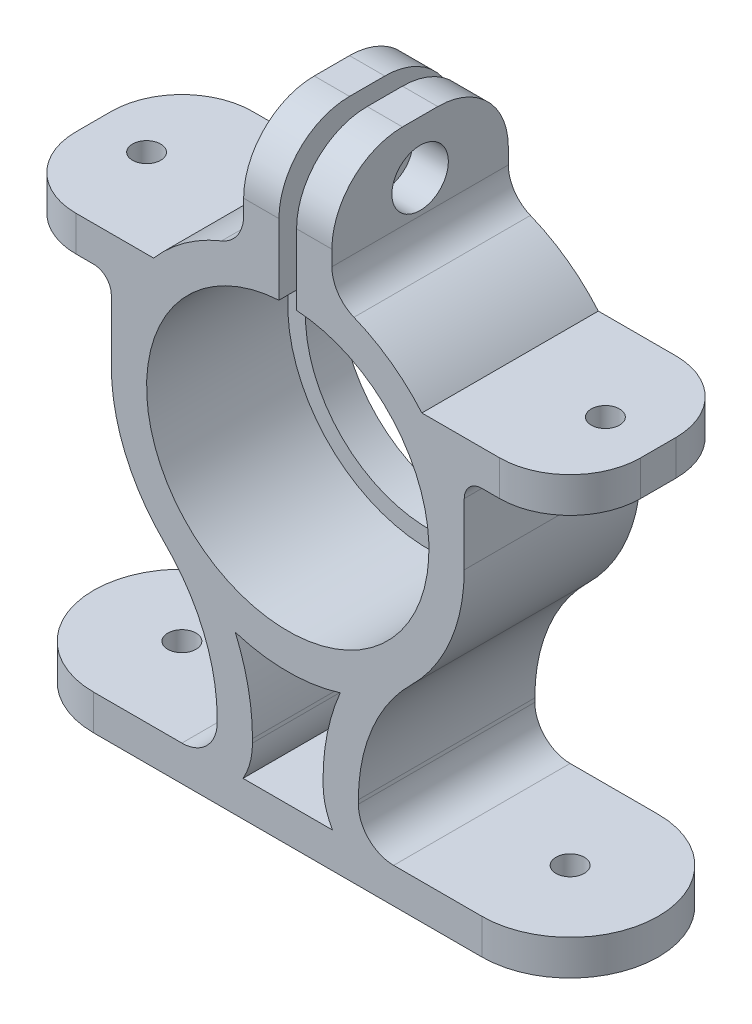
SolidWorks part; units mm, degrees
ref_plane "Front Plane" through (0, 0, 0) normal (0, 0, 1) x (1, 0, 0)
ref_plane "Top Plane" through (0, 0, 0) normal (0, 1, 0) x (1, 0, 0)
ref_plane "Right Plane" through (0, 0, 0) normal (1, 0, 0) x (0, 0, -1)
sketch "Sketch1" plane through (0, 0, 0) normal (0, 0, 1) x (1, 0, 0)
  line L0 (0, 0) -> (65.6061, 0) construction
  line L1 (32.8031, 0) -> (32.8031, 18.5) construction
  line L2 (12.0204, 18.5) -> (55.4995, 18.5) construction
  line L3 (16.803, 0) -> (48.8031, 0)
  line L4 (32.3031, 26.4843) -> (32.3031, 34.4875)
  line L5 (13.0695, 25) -> (55.8846, 25) construction
  line L6 (33.3031, 26.4843) -> (33.3031, 34.4875)
  line L7 (33.3031, 34.4875) -> (35.3032, 34.4875)
  line L8 (35.3032, 34.4875) -> (35.3032, 29.6243)
  line L9 (32.3031, 34.4875) -> (30.3031, 34.4875)
  line L10 (30.3031, 34.4875) -> (30.3031, 29.6243)
  line L11 (22.803, 22) -> (22.803, 18.5)
  line L12 (48.8031, 0) -> (48.8031, 2)
  line L13 (42.8031, 22) -> (42.8031, 18.5)
  line L14 (21.5003, 25) -> (16.803, 25)
  line L15 (16.803, 25) -> (16.803, 23)
  line L16 (16.803, 23) -> (21.803, 23)
  line L17 (44.1058, 25) -> (48.8031, 25)
  line L18 (48.8031, 23) -> (43.8031, 23)
  line L19 (48.8031, 25) -> (48.8031, 23)
  line L20 (16.803, 2) -> (26.803, 2)
  line L21 (16.803, 2) -> (16.803, 0)
  line L22 (28.803, 4) -> (28.803, 4.2171)
  line L23 (48.8031, 2) -> (38.8031, 2)
  line L24 (36.8031, 4) -> (36.8031, 4.2171)
  line L25 (44.1058, 25) -> (40.4025, 25)
  line L26 (21.5003, 25) -> (25.2036, 25)
  line L27 (35.7769, 8.9524) -> (35.7769, 8.9524)
  line L28 (35.7769, 8.9524) -> (35.7769, 8.9524)
  line L29 (35.7769, 8.9524) -> (35.7769, 8.9524)
  line L30 (35.7769, 8.9524) -> (35.7769, 8.9524)
  line L31 (35.7769, 8.9524) -> (35.7769, 8.9524)
  line L32 (35.7769, 8.9524) -> (35.7769, 8.9524)
  line L33 (35.7769, 8.9524) -> (35.7769, 8.9524)
  line L34 (35.7769, 8.9524) -> (35.7769, 8.9524)
  line L35 (34.8031, 4) -> (34.8031, 4.2171)
  line L36 (35.339, 2) -> (35.339, 2)
  line L37 (35.339, 2) -> (35.339, 2)
  line L38 (30.2671, 2) -> (35.339, 2)
  line L39 (30.2671, 2) -> (30.2671, 2)
  line L40 (30.2671, 2) -> (30.2671, 2)
  line L41 (30.803, 4) -> (30.803, 4.2171)
  line L42 (29.8292, 8.9524) -> (29.8292, 8.9524)
  line L43 (29.8292, 8.9524) -> (29.8292, 8.9524)
  line L44 (29.8292, 8.9524) -> (29.8292, 8.9524)
  line L45 (29.8292, 8.9524) -> (29.8292, 8.9524)
  line L46 (29.8292, 8.9524) -> (29.8292, 8.9524)
  line L47 (29.8292, 8.9524) -> (29.8292, 8.9524)
  line L48 (29.8292, 8.9524) -> (29.8292, 8.9524)
  line L49 (29.8292, 8.9524) -> (29.8292, 8.9524)
  arc A0 (32.3031, 26.4843) -> (33.3031, 26.4843) centre (32.8031, 18.5) ccw
  arc A1 (29.8292, 8.9524) -> (35.7769, 8.9524) centre (32.8031, 18.5) ccw
  arc A2 (35.7769, 8.9524) -> (35.7769, 8.9524) centre (35.7769, 8.9524) ccw
  arc A3 (35.7769, 8.9524) -> (35.7769, 8.9524) centre (35.7769, 8.9524) cw
  arc A4 (35.7769, 8.9524) -> (35.7769, 8.9524) centre (35.7769, 8.9524) ccw
  arc A5 (28.803, 4.2171) -> (25.803, 11.3585) centre (18.803, 4.2171) ccw
  arc A6 (36.8031, 4.2171) -> (39.8031, 11.3585) centre (46.8031, 4.2171) cw
  arc A7 (29.053, 27.7703) -> (25.2036, 25) centre (32.8031, 18.5) ccw
  arc A8 (39.8031, 11.3585) -> (42.8031, 18.5) centre (32.8031, 18.5) ccw
  arc A9 (26.803, 2) -> (28.803, 4) centre (26.803, 4) ccw
  arc A10 (38.8031, 2) -> (36.8031, 4) centre (38.8031, 4) cw
  arc A11 (35.3032, 29.6243) -> (36.5532, 27.7702) centre (37.3032, 29.6243) ccw
  arc A12 (30.3031, 29.6243) -> (29.053, 27.7703) centre (28.3031, 29.6243) cw
  arc A13 (43.8031, 23) -> (42.8031, 22) centre (43.8031, 22) ccw
  arc A14 (21.803, 23) -> (22.803, 22) centre (21.803, 22) cw
  arc A15 (40.4025, 25) -> (36.5532, 27.7702) centre (32.8031, 18.5) ccw
  arc A16 (22.803, 18.5) -> (25.803, 11.3585) centre (32.8031, 18.5) ccw
  arc A17 (35.7769, 8.9524) -> (35.7769, 8.9524) centre (35.7769, 8.9524) ccw
  arc A18 (34.8031, 4.2171) -> (35.7769, 8.9524) centre (46.8031, 4.2171) cw
  arc A19 (35.339, 2) -> (34.8031, 4) centre (38.8031, 4) cw
  arc A20 (30.2671, 2) -> (30.803, 4) centre (26.803, 4) ccw
  arc A21 (30.803, 4.2171) -> (29.8292, 8.9524) centre (18.803, 4.2171) ccw
  arc A22 (29.8292, 8.9524) -> (29.8292, 8.9524) centre (29.8292, 8.9524) ccw
  arc A23 (29.8292, 8.9524) -> (29.8292, 8.9524) centre (29.8292, 8.9524) cw
  arc A24 (29.8292, 8.9524) -> (29.8292, 8.9524) centre (29.8292, 8.9524) cw
  arc A25 (29.8292, 8.9524) -> (29.8292, 8.9524) centre (29.8292, 8.9524) cw
  point P39 (36.8031, 9.3348)
  point P42 (40.4025, 25)
  point P45 (25.2036, 25)
  point P48 (28.803, 2)
  dimension "D2" = 2
  dimension "D1" = 10
  dimension "D3" = 1
  dimension "D4" = 2
extrude "Boss-Extrude1" add sketch "Sketch1" along normal blind 10
sketch "Sketch3" plane through (0, 2, 0) normal (0, 1, 0) x (1, 0, 0)
  line L2 (43.8031, -10) -> (48.8031, -10)
  line L3 (48.8031, -10) -> (38.8031, -10) construction
  line L4 (48.8031, -10) -> (48.8031, 0)
  line L5 (48.8031, 0) -> (43.8031, 0)
  arc A0 (43.8031, -10) -> (43.8031, 0) centre (43.8031, -5) ccw
  circle A1 centre (43.8031, -5) radius 0.8
  line M1 (48.8031, 0) -> (38.8031, 0)
  line M3 (38.8031, -10) -> (48.8031, -10)
  line M4 (48.8031, -10) -> (48.8031, 0)
extrude "Cut-Extrude1" cut sketch "Sketch3" against normal blind 2 contours A0 M3 M4 | A0 L4 M1 | A1 region at (47.6863, 2, 8.8832) region at (47.6863, 2, 1.1168) region at (43.8031, 2, 5)
sketch "Sketch4" plane through (0, 2, 0) normal (0, 1, 0) x (1, 0, 0)
  line L0 (21.803, -10) -> (16.803, -10)
  line L1 (16.803, -10) -> (16.803, 0)
  line L2 (16.803, 0) -> (21.803, 0)
  arc A0 (21.803, 0) -> (21.803, -10) centre (21.803, -5) ccw
  circle A1 centre (21.803, -5) radius 0.8
  line M1 (26.803, 0) -> (16.803, 0)
  line M2 (16.803, 0) -> (16.803, -10)
  line M3 (16.803, -10) -> (26.803, -10)
extrude "Cut-Extrude2" cut sketch "Sketch4" against normal blind 2 contours A0 L1 M3 | A0 M1 M2 | A1 region at (17.9198, 2, 1.1168) region at (17.9198, 2, 8.8832) region at (21.803, 2, 5)
sketch "Sketch5" plane through (0, 25, 0) normal (0, 1, 0) x (1, 0, 0)
  line L0 (20.803, -10) -> (16.803, -10)
  line L1 (16.803, -10) -> (16.803, -6)
  line L2 (16.803, -4) -> (16.803, 0)
  line L3 (16.803, 0) -> (20.803, 0)
  line L4 (44.8031, 0) -> (48.8031, 0)
  line L5 (48.8031, 0) -> (48.8031, -4)
  line L6 (48.8031, -6) -> (48.8031, -10)
  line L7 (48.8031, -10) -> (44.8031, -10)
  arc A0 (44.8031, 0) -> (48.8031, -4) centre (44.8031, -4) cw
  arc A1 (48.8031, -6) -> (44.8031, -10) centre (44.8031, -6) cw
  arc A2 (20.803, -10) -> (16.803, -6) centre (20.803, -6) cw
  arc A3 (16.803, -4) -> (20.803, 0) centre (20.803, -4) cw
  circle A4 centre (19.803, -5) radius 0.8
  circle A5 centre (45.8031, -5) radius 0.8
  point P10 (48.8031, 0)
  point P13 (48.8031, -10)
  point P16 (16.803, -10)
  point P19 (16.803, 0)
  dimension "D1" = 4
extrude "Cut-Extrude3" cut sketch "Sketch5" against normal blind 2
ref_axis "Axis1" through (19.803, 19.7556, 5) along (0, 1, 0)
ref_axis "Axis2" through (45.8031, 20.1662, 5) along (0, 1, 0)
ref_axis "Axis3" through (43.8031, -1.9714, 5) along (0, 1, 0)
ref_axis "Axis4" through (21.803, -1.9098, 5) along (0, 1, 0)
ref_axis "Axis5" through (32.8031, 18.5, 14.0547) along (0, 0, -1)
sketch "Sketch6" plane through (30.3031, 0, 0) normal (-1, 0, 0) x (0, 0, 1)
  circle A0 centre (5, 31.4875) radius 0.8
extrude "Cut-Extrude4" cut sketch "Sketch6" against normal blind 3
sketch "Sketch7" plane through (35.3032, 0, 0) normal (1, 0, 0) x (0, 0, -1)
  circle A0 centre (-5, 31.4875) radius 1.6
extrude "Cut-Extrude5" cut sketch "Sketch7" against normal blind 3
ref_axis "Axis6" through (27.0571, 31.4875, 5) along (1, 0, 0)
sketch "Sketch8" plane through (30.3031, 0, 0) normal (-1, 0, 0) x (0, 0, 1)
  line L0 (0, 30.4875) -> (0, 34.4875)
  line L1 (0, 34.4875) -> (4, 34.4875)
  line L2 (6, 34.4875) -> (10, 34.4875)
  line L3 (10, 34.4875) -> (10, 30.4875)
  arc A0 (6, 34.4875) -> (10, 30.4875) centre (6, 30.4875) cw
  arc A1 (0, 30.4875) -> (4, 34.4875) centre (4, 30.4875) cw
  point P10 (10, 34.4875)
  point P13 (0, 34.4875)
  dimension "D1" = 4
extrude "Cut-Extrude6" cut sketch "Sketch8" against normal blind 10
sketch "Sketch9" plane through (0, 0, 0) normal (0, 0, -1) x (-1, 0, 0)
  line L0 (-33.3031, 26.4843) -> (-33.3031, 25.4821)
  line L1 (-32.3031, 26.4843) -> (-32.3031, 25.4821)
  arc A0 (-33.3031, 26.4843) -> (-32.3031, 26.4843) centre (-32.8031, 18.5) ccw
  arc A1 (-33.3031, 25.4821) -> (-32.3031, 25.4821) centre (-32.8031, 18.5) ccw
extrude "Boss-Extrude2" add sketch "Sketch9" against normal blind 2
